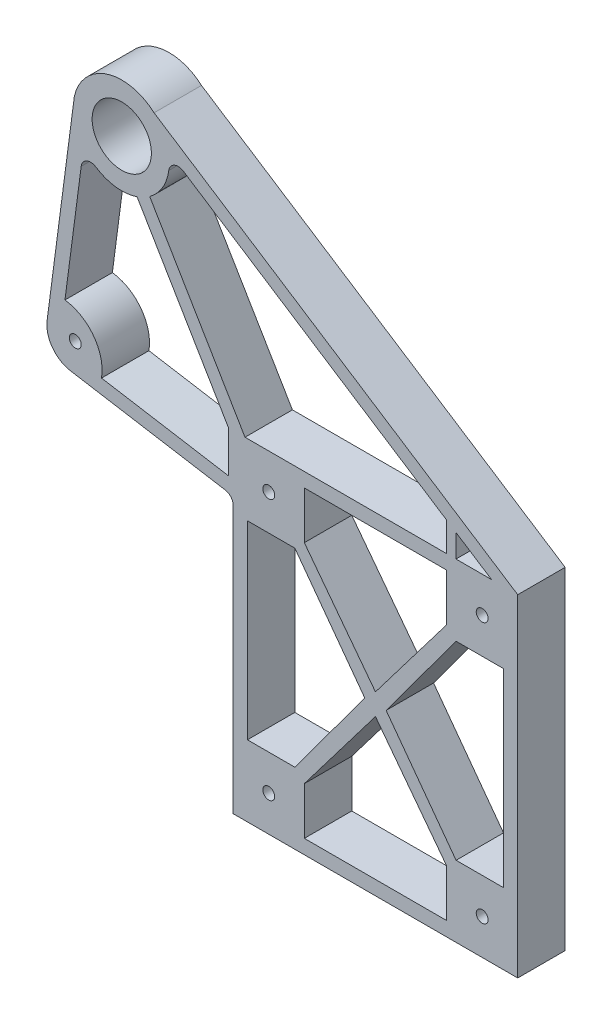
SolidWorks part; units mm, degrees
material "Magnesium Alloy"
ref_plane "Front Plane" through (0, 0, 0) normal (0, 0, 1) x (1, 0, 0)
ref_plane "Top Plane" through (0, 0, 0) normal (0, 1, 0) x (1, 0, 0)
ref_plane "Right Plane" through (0, 0, 0) normal (1, 0, 0) x (0, 0, -1)
sketch "Sketch1" plane through (0, 0, 0) normal (0, 0, 1) x (1, 0, 0)
  line L0 (0, 0) -> (76.2, 0)
  line L1 (76.2, 0) -> (76.2, 88.9)
  line L2 (76.2, 88.9) -> (-21.1908, 151.9642)
  line L3 (0, 0) -> (0, 73.66)
  line L4 (0, 73.66) -> (-50.8, 82.1364)
  line L5 (-50.8, 82.1364) -> (-42.545, 145.0975)
  arc A0 (-21.1908, 151.9642) -> (-42.545, 145.0975) centre (-29.845, 142.24) ccw
  circle A1 centre (-29.845, 142.24) radius 7.9375
  dimension "D5" = 15.875
  dimension "D6" = 5.08
  dimension "D1" = 76.2
  dimension "D2" = 88.9
  dimension "D3" = 29.845
  dimension "D4" = 142.24
  dimension "D7" = 63.5
  dimension "D8" = 15.24
  dimension "D9" = 12.7
  dimension "D10" = 50.8
extrude "Boss-Extrude1" add sketch "Sketch1" along normal blind 12.7
ref_axis "Axis1" through (-29.845, 142.24, 12.7) along (0, 0, -1)
sketch "Sketch2" plane through (0, 0, 12.7) normal (0, 0, 1) x (1, 0, 0)
  line L0 (19.05, 3.81) -> (57.15, 3.81)
  line L1 (57.15, 3.81) -> (57.15, 16.51)
  line L2 (57.15, 16.51) -> (38.1, 41.5925)
  line L3 (38.1, 41.5925) -> (19.05, 16.51)
  line L4 (19.05, 16.51) -> (19.05, 3.81)
  line L5 (3.81, 19.05) -> (16.51, 19.05)
  line L6 (16.51, 19.05) -> (35.2425, 44.45)
  line L7 (35.2425, 44.45) -> (16.51, 69.85)
  line L8 (16.51, 69.85) -> (3.81, 69.85)
  line L9 (3.81, 69.85) -> (3.81, 19.05)
  line L10 (19.05, 85.09) -> (19.05, 72.39)
  line L11 (19.05, 72.39) -> (38.1, 47.3075)
  line L12 (38.1, 47.3075) -> (57.15, 72.39)
  line L13 (57.15, 72.39) -> (57.15, 85.09)
  line L14 (57.15, 85.09) -> (19.05, 85.09)
  line L15 (72.39, 69.85) -> (59.69, 69.85)
  line L16 (59.69, 69.85) -> (40.9575, 44.45)
  line L17 (40.9575, 44.45) -> (59.69, 19.05)
  line L18 (59.69, 19.05) -> (72.39, 19.05)
  line L19 (72.39, 19.05) -> (72.39, 69.85)
  line L20 (76.2, 0) -> (76.2, 88.9) construction
  line L21 (0, 0) -> (76.2, 0) construction
  line L22 (0, 73.66) -> (0, 0) construction
  dimension "D1" = 3.81
  dimension "D2" = 12.7
  dimension "D3" = 3.81
  dimension "D4" = 3.81
  dimension "D5" = 3.81
  dimension "D6" = 19.05
  dimension "D7" = 19.05
  dimension "D8" = 19.05
  dimension "D9" = 19.05
  dimension "D10" = 5.715
  dimension "D11" = 5.715
extrude "Cut-Extrude1" cut sketch "Sketch2" against normal blind 12.7
sketch "Sketch3" plane through (0, 0, 12.7) normal (0, 0, 1) x (1, 0, 0)
  line L0 (76.2, 0) -> (76.2, 88.9) construction
  line L1 (0, 0) -> (76.2, 0) construction
  line L2 (0, 73.66) -> (0, 0) construction
  circle A0 centre (66.675, 79.375) radius 1.5875
  circle A1 centre (9.525, 79.375) radius 1.5875
  circle A2 centre (9.525, 9.525) radius 1.5875
  circle A3 centre (66.675, 9.525) radius 1.5875
  dimension "D5" = 3.175
  dimension "D1" = 9.525
  dimension "D2" = 9.525
  dimension "D3" = 9.525
  dimension "D4" = 9.525
extrude "Cut-Extrude2" cut sketch "Sketch3" against normal blind 12.7
sketch "Sketch4" plane through (0, 0, 12.7) normal (0, 0, 1) x (1, 0, 0)
  line L0 (69.1903, 88.9) -> (-17.449, 145.0022)
  line L1 (69.1903, 88.9) -> (3.1586, 88.9)
  line L2 (3.1586, 88.9) -> (-22.365, 131.9765)
  line L3 (-40.0655, 134.7013) -> (-45.0582, 96.6219)
  line L4 (-35.2699, 83.4077) -> (-1.27, 77.7346)
  line L5 (-1.27, 77.7346) -> (-1.27, 88.9)
  line L6 (-1.27, 88.9) -> (-25.7515, 130.2178)
  line L7 (76.2, 88.9) -> (-21.1908, 151.9642) construction
  line L8 (-50.8, 82.1364) -> (0, 73.66) construction
  line L9 (0, 73.66) -> (0, 0) construction
  line L10 (-42.545, 145.0975) -> (-50.8, 82.1364) construction
  arc A0 (-17.449, 145.0022) -> (-22.365, 131.9765) centre (-29.845, 142.24) cw
  arc A1 (-40.0655, 134.7013) -> (-25.7515, 130.2178) centre (-29.845, 142.24) ccw
  arc A2 (-35.2699, 83.4077) -> (-45.0582, 96.6219) centre (-46.5441, 85.2889) ccw
  dimension "D1" = 12.7
  dimension "D2" = 12.7
  dimension "D9" = 11.43
  dimension "D3" = 3.81
  dimension "D4" = 3.81
  dimension "D5" = 1.27
  dimension "D6" = 3.81
  dimension "D7" = 3.81
  dimension "D8" = 3.81
  dimension "D10" = 3.81
extrude "Cut-Extrude3" cut sketch "Sketch4" against normal blind 12.7
fillet "Fillet1" radius 2.54 2 edges at (-17.449, 145.0022, 6.35) (-40.0655, 134.7013, 6.35)
sketch "Sketch5" plane through (0, 0, 12.7) normal (0, 0, 1) x (1, 0, 0)
  line L0 (57.1253, 88.9) -> (59.6653, 88.9)
  line L1 (3.1586, 88.9) -> (69.1903, 88.9) construction
  line L2 (59.6653, 88.9) -> (59.6653, 95.0678)
  line L3 (69.1903, 88.9) -> (-13.3587, 142.3536) construction
  line L4 (59.6653, 95.0678) -> (57.1253, 96.7125)
  line L5 (57.1253, 96.7125) -> (57.1253, 88.9)
  dimension "D1" = 2.54
  dimension "D2" = 9.525
extrude "Boss-Extrude2" add sketch "Sketch5" against normal blind 12.7
sketch "Sketch6" plane through (0, 0, 12.7) normal (0, 0, 1) x (1, 0, 0)
  line L0 (-50.8, 82.1364) -> (0, 73.66) construction
  line L1 (-42.545, 145.0975) -> (-50.8, 82.1364) construction
  circle A0 centre (-42.2881, 88.4414) radius 1.5875
  dimension "D3" = 3.175
  dimension "D1" = 7.62
  dimension "D2" = 7.62
extrude "Cut-Extrude4" cut sketch "Sketch6" against normal blind 12.7
fillet "Fillet2" radius 7.62 1 edges at (-50.8, 82.1364, 6.35)
ref_axis "Axis2" through (-42.2881, 88.4414, 0) along (0, 0, 1)
fillet "Fillet3" radius 2.54 1 edges at (0, 73.66, 6.35)
